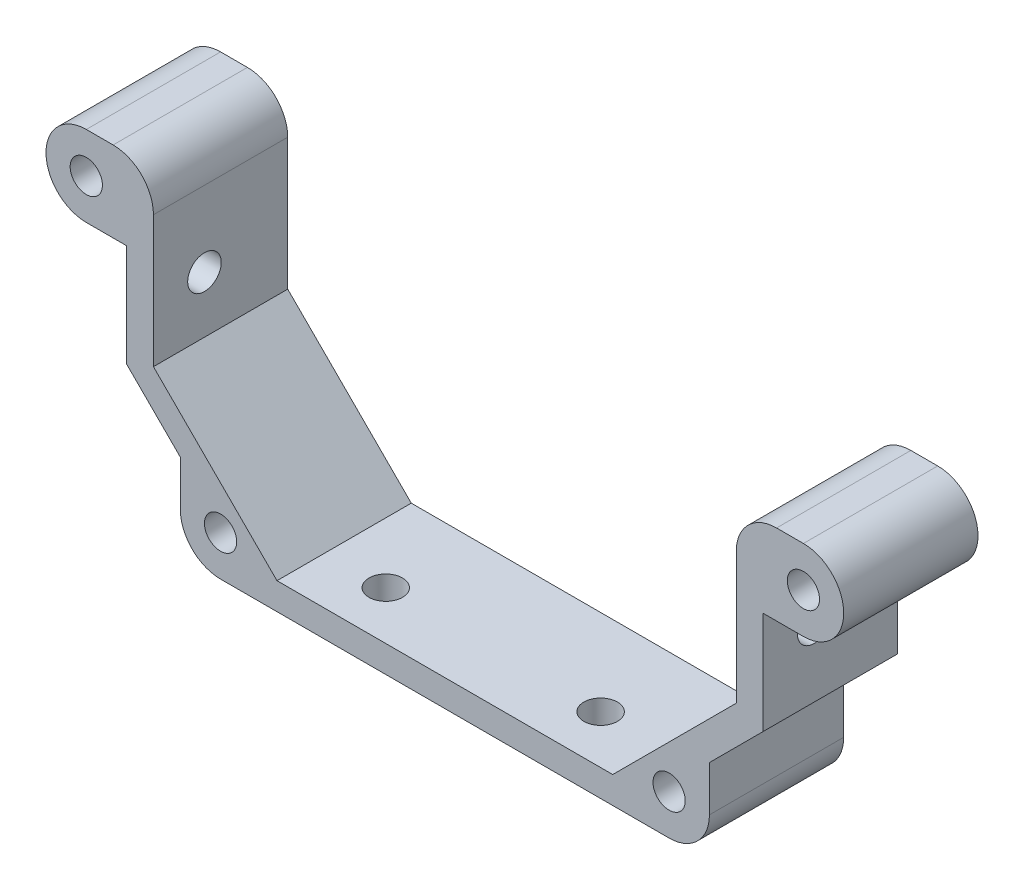
SolidWorks part; units mm, degrees
ref_plane "前视基准面" through (0, 0, 0) normal (0, 0, 1) x (1, 0, 0)
ref_plane "上视基准面" through (0, 0, 0) normal (0, 1, 0) x (1, 0, 0)
ref_plane "右视基准面" through (0, 0, 0) normal (1, 0, 0) x (0, 0, -1)
sketch "草图1" plane through (0, 0, 0) normal (0, 0, 1) x (1, 0, 0)
  line L0 (0, 0) -> (25, 0)
  line L1 (12.5, 0) -> (12.5, 38.9926) construction
  line L2 (0, 0) -> (-9.2, 9.2)
  line L3 (-9.2, 9.2) -> (-9.2, 16.4)
  line L4 (25, 0) -> (34.2, 9.2)
  line L5 (34.2, 9.2) -> (34.2, 16.4)
  line L6 (-9.2, 16.4) -> (-11.2, 16.4)
  line L7 (-11.2, 16.4) -> (-11.2, 8.3716)
  line L8 (-11.2, 8.3716) -> (-0.8284, -2)
  line L9 (-0.8284, -2) -> (25.8284, -2)
  line L10 (36.2, 8.3716) -> (25.8284, -2)
  line L11 (36.2, 16.4) -> (36.2, 8.3716)
  line L12 (34.2, 16.4) -> (36.2, 16.4)
  dimension "D1" = 135
  dimension "D2" = 25
  dimension "D3" = 43.4
  dimension "D4" = 16.4
  dimension "D5" = 2
  dimension "D6" = 2
  dimension "D7" = 2
extrude "凸台-拉伸1" add sketch "草图1" along normal blind 10
sketch "草图2" plane through (0, -2, 0) normal (0, -1, 0) x (1, 0, 0)
  line L0 (4.5, 6.4) -> (20.5, 6.4) construction
  line L1 (-0.8284, 0) -> (25.8284, 0) construction
  line L2 (12.5, 10) -> (12.5, 0) construction
  line L3 (-0.8284, 10) -> (25.8284, 10) construction
  circle A0 centre (4.5, 6.4) radius 1.25
  circle A1 centre (20.5, 6.4) radius 1.25
  point P8 (12.5, 6.4)
  dimension "D3" = 2.5
  dimension "D1" = 6.4
  dimension "D2" = 16
extrude "切除-拉伸1" cut sketch "草图2" against normal through all and the other way through all
sketch "草图3" plane through (-11.2, 0, 0) normal (-1, 0, 0) x (0, 0, 1)
  line L0 (0, 16.4) -> (0, 8.3716) construction
  line L1 (10, 16.4) -> (0, 16.4) construction
  circle A0 centre (6.2, 13.4) radius 1.25
  dimension "D1" = 6.2
  dimension "D3" = 2.5
  dimension "D2" = 3
extrude "切除-拉伸2" cut sketch "草图3" against normal through all
sketch "草图4" plane through (0, 0, 10) normal (0, 0, 1) x (1, 0, 0)
  line L0 (-7.2, 4.3716) -> (-7.2, 1)
  line L1 (-4.2, -2) -> (-0.8284, -2)
  line L2 (-11.2, 8.3716) -> (-0.8284, -2) construction
  line L3 (-0.8284, -2) -> (-7.2, 4.3716)
  line L4 (12.5, 0) -> (12.5, -2) construction
  line L5 (25, 0) -> (0, 0) construction
  line L6 (-0.8284, -2) -> (25.8284, -2) construction
  line L7 (29.2, -2) -> (25.8284, -2)
  line L8 (32.2, 4.3716) -> (32.2, 1)
  line L9 (25.8284, -2) -> (32.2, 4.3716)
  line L10 (-11.2, 16.4) -> (-11.2, 8.3716) construction
  arc A0 (-7.2, 1) -> (-4.2, -2) centre (-4.2, 1) ccw
  arc A1 (32.2, 1) -> (29.2, -2) centre (29.2, 1) cw
  dimension "D1" = 3
  dimension "D2" = 4
extrude "凸台-拉伸2" add sketch "草图4" against normal up to surface (10 mm away) up to face at (12.5, 8.0619, 0)
sketch "草图5" plane through (0, 0, 10) normal (0, 0, 1) x (1, 0, 0)
  circle A0 centre (-4.2, 1) radius 1.2
  circle A1 centre (29.2, 1) radius 1.2
  dimension "D1" = 2.4
extrude "切除-拉伸3" cut sketch "草图5" against normal through all
cosmetic thread "装饰螺纹线1" parameters "D2"=3
cosmetic thread "装饰螺纹线2" parameters "D2"=3
sketch "草图6" plane through (0, 0, 10) normal (0, 0, 1) x (1, 0, 0)
  line L0 (12.5, 0) -> (12.5, -2) construction
  line L1 (25, 0) -> (0, 0) construction
  line L2 (-4.2, -2) -> (29.2, -2) construction
  line L4 (-12.2, 22) -> (-14.2, 22)
  line L10 (-9.2, 9.2) -> (-9.2, 16.4) construction
  line L11 (-9.2, 19) -> (-9.2, 16.4)
  line L12 (-14.2, 16) -> (-11.2, 16)
  line L13 (-11.2, 16.4) -> (-11.2, 8.3716) construction
  line L14 (-11.2, 16) -> (-11.2, 16.4)
  line L15 (-11.2, 16.4) -> (-9.2, 16.4)
  line L16 (36.2, 16) -> (36.2, 16.4)
  line L17 (39.2, 16) -> (36.2, 16)
  line L18 (37.2, 22) -> (39.2, 22)
  line L19 (34.2, 19) -> (34.2, 16.4)
  line L20 (36.2, 16.4) -> (34.2, 16.4)
  circle A0 centre (-14.2, 19) radius 1.2
  arc A1 (-14.2, 22) -> (-14.2, 16) centre (-14.2, 19) ccw
  circle A2 centre (-4.2, 1) radius 1.2 construction
  arc A5 (-12.2, 22) -> (-9.2, 19) centre (-12.2, 19) cw
  arc A6 (39.2, 22) -> (39.2, 16) centre (39.2, 19) cw
  arc A7 (37.2, 22) -> (34.2, 19) centre (37.2, 19) ccw
  circle A8 centre (39.2, 19) radius 1.2
  dimension "D1" = 3
  dimension "D3" = 5
  dimension "D2" = 18
extrude "凸台-拉伸3" add sketch "草图6" against normal up to surface (10 mm away) up to face at (-3, 1, 0)
cosmetic thread "装饰螺纹线7" parameters "D2"=3
cosmetic thread "装饰螺纹线8" parameters "D2"=3
